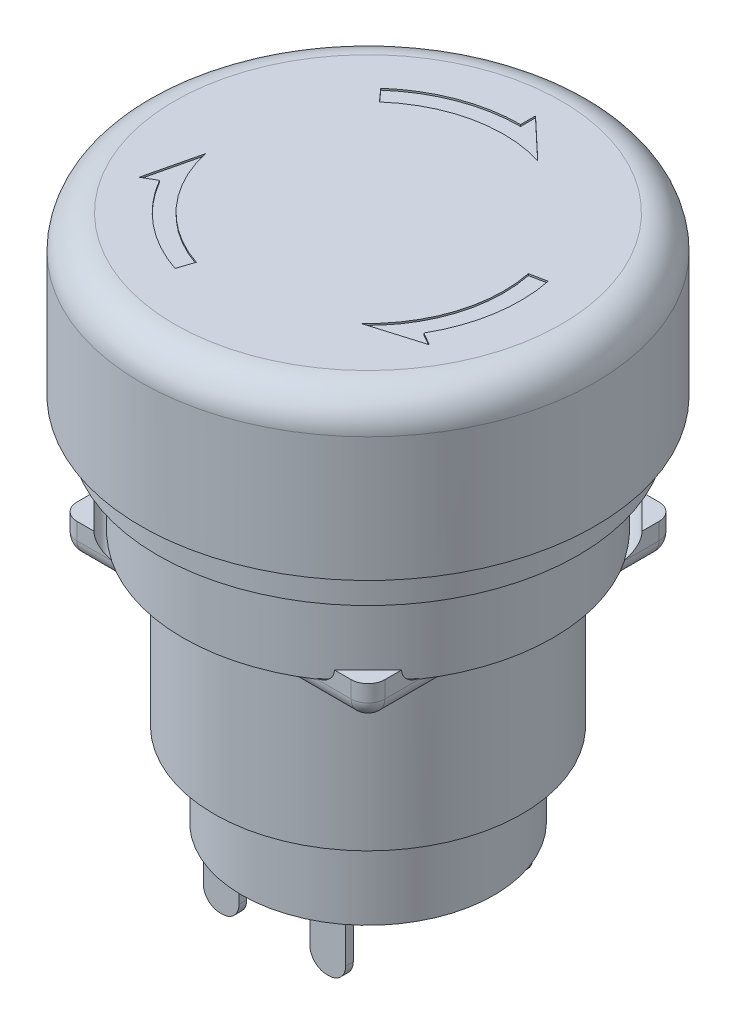
SolidWorks part; units mm, degrees
ref_plane "前视基准面" through (0, 0, 0) normal (0, 0, 1) x (1, 0, 0)
ref_plane "上视基准面" through (0, 0, 0) normal (0, 1, 0) x (1, 0, 0)
ref_plane "右视基准面" through (0, 0, 0) normal (1, 0, 0) x (0, 0, -1)
sketch "草图1" plane through (0, 0, 0) normal (0, 1, 0) x (1, 0, 0)
  circle A0 centre (0, 0) radius 7.5
  dimension "D1" = 15
extrude "凸台-拉伸1" add sketch "草图1" along normal blind 5
sketch "草图2" plane through (0, 0, 0) normal (0, -1, 0) x (1, 0, 0)
  line L0 (0, 0) -> (0, 7.5) construction
  line L1 (-4.2318, 5.5619) -> (-2.1076, 5.5619)
  line L2 (-4.2318, 5.5619) -> (-4.2318, 5.1067)
  line L3 (-4.2318, 5.1067) -> (-2.1076, 5.1067)
  line L4 (-2.1076, 5.5619) -> (-2.1076, 5.1067)
  line L5 (-4.2318, 5.5619) -> (-2.1076, 5.1067) construction
  line L6 (-4.2318, 5.1067) -> (-2.1076, 5.5619) construction
  line L7 (0, 0) -> (-7.5, 0) construction
  line L8 (4.2318, 5.1067) -> (2.1076, 5.5619) construction
  line L9 (4.2318, 5.5619) -> (2.1076, 5.1067) construction
  line L10 (2.1076, 5.5619) -> (2.1076, 5.1067)
  line L11 (4.2318, 5.1067) -> (2.1076, 5.1067)
  line L12 (4.2318, 5.5619) -> (4.2318, 5.1067)
  line L13 (4.2318, 5.5619) -> (2.1076, 5.5619)
  line L14 (4.2318, -5.5619) -> (2.1076, -5.1067) construction
  line L15 (4.2318, -5.1067) -> (2.1076, -5.5619) construction
  line L16 (4.2318, -5.5619) -> (2.1076, -5.5619)
  line L17 (4.2318, -5.5619) -> (4.2318, -5.1067)
  line L18 (2.1076, -5.5619) -> (2.1076, -5.1067)
  line L19 (-4.2318, -5.1067) -> (-2.1076, -5.5619) construction
  line L20 (-4.2318, -5.5619) -> (-2.1076, -5.1067) construction
  line L21 (-2.1076, -5.5619) -> (-2.1076, -5.1067)
  line L22 (-4.2318, -5.5619) -> (-4.2318, -5.1067)
  line L23 (-4.2318, -5.5619) -> (-2.1076, -5.5619)
  line L24 (4.2318, -5.1067) -> (2.1076, -5.1067)
  line L25 (-4.2318, -5.1067) -> (-2.1076, -5.1067)
  circle A0 centre (0, 0) radius 7.5 construction
  point P0 (-3.1697, 5.3343)
  point P16 (3.1697, 5.3343)
  point P21 (3.1697, -5.3343)
  point P26 (-3.1697, -5.3343)
extrude "凸台-拉伸2" add sketch "草图2" along normal blind 3.5
fillet "圆角1" radius 1 8 edges at (-4.2318, -3.5, -5.3343) (-2.1076, -3.5, -5.3343) (2.1076, -3.5, -5.3343) (4.2318, -3.5, -5.3343) (4.2318, -3.5, 5.3343) (2.1076, -3.5, 5.3343) (-2.1076, -3.5, 5.3343) (-4.2318, -3.5, 5.3343)
sketch "草图4" plane through (0, 5, 0) normal (0, 1, 0) x (1, 0, 0)
  circle A0 centre (0, 0) radius 9.15
  dimension "D1" = 18.3
extrude "凸台-拉伸3" add sketch "草图4" along normal blind 9
sketch "草图5" plane through (0, 14, 0) normal (0, 1, 0) x (1, 0, 0)
  line L1 (9.15, -9.15) -> (-9.15, -9.15)
  line L2 (9.15, -9.15) -> (9.15, 9.15)
  line L3 (9.15, 9.15) -> (-9.15, 9.15)
  line L4 (-9.15, -9.15) -> (-9.15, 9.15)
  line L5 (9.15, -9.15) -> (-9.15, 9.15) construction
  line L6 (9.15, 9.15) -> (-9.15, -9.15) construction
  circle A0 centre (0, 0) radius 9.15 construction
  point P0 (0, 0)
extrude "凸台-拉伸4" add sketch "草图5" along normal blind 1
sketch "草图6" plane through (0, 15, 0) normal (0, 1, 0) x (1, 0, 0)
  line L0 (-9.15, 9.15) -> (-7.15, 9.15)
  line L1 (9.15, 9.15) -> (-9.15, 9.15) construction
  line L2 (-7.15, 9.15) -> (-9.15, 7.15)
  line L3 (-9.15, 9.15) -> (-9.15, -9.15) construction
  line L4 (-9.15, 7.15) -> (-9.15, 9.15)
  line L5 (0, 0) -> (0, 7.15) construction
  line L6 (0, 0) -> (-9.15, 0) construction
  line L7 (9.15, 7.15) -> (9.15, 9.15)
  line L8 (7.15, 9.15) -> (9.15, 7.15)
  line L9 (9.15, 9.15) -> (7.15, 9.15)
  line L10 (9.15, -9.15) -> (7.15, -9.15)
  line L11 (7.15, -9.15) -> (9.15, -7.15)
  line L12 (9.15, -7.15) -> (9.15, -9.15)
  line L13 (-9.15, -7.15) -> (-9.15, -9.15)
  line L14 (-7.15, -9.15) -> (-9.15, -7.15)
  line L15 (-9.15, -9.15) -> (-7.15, -9.15)
  dimension "D1" = 2
  dimension "D2" = 2
extrude "凸台-拉伸5" add sketch "草图6" along normal blind 1
fillet "圆角2" radius 1 4 edges at (8.15, 15, 8.15) (8.15, 15, -8.15) (-8.15, 15, -8.15) (-8.15, 15, 8.15)
fillet "圆角3" radius 1 4 edges at (9.15, 15, -9.15) (-9.15, 15, -9.15) (-9.15, 15, 9.15) (9.15, 15, 9.15)
fillet "圆角4" radius 1 12 edges at (-4.075, 14, 9.15) (4.075, 14, 9.15) (8.8571, 14, 8.8571) (9.15, 14, 4.075) (9.15, 14, -4.075) (8.8571, 14, -8.8571) (4.075, 14, -9.15) (-4.075, 14, -9.15) (-8.8571, 14, -8.8571) (-9.15, 14, -4.075) (-9.15, 14, 4.075) (-8.8571, 14, 8.8571)
sketch "草图7" plane through (0, 15, 0) normal (0, 1, 0) x (1, 0, 0)
  circle A0 centre (0, 0) radius 11
  dimension "D1" = 22
extrude "凸台-拉伸6" add sketch "草图7" along normal blind 5
sketch "草图8" plane through (0, 20, 0) normal (0, 1, 0) x (1, 0, 0)
  circle A0 centre (0, 0) radius 13.5
  dimension "D1" = 27
extrude "凸台-拉伸7" add sketch "草图8" along normal blind 11.4
fillet "圆角5" radius 2 1 edges at (0, 31.4, 13.5)
sketch "草图9" plane through (0, 20, 0) normal (0, -1, 0) x (1, 0, 0)
  circle A0 centre (0, 0) radius 12.5
  dimension "D1" = 25
extrude "切除-拉伸1" cut sketch "草图9" against normal blind 2 flip side to cut
sketch "草图10" plane through (0, 31.4, 0) normal (0, 1, 0) x (1, 0, 0)
  line L0 (0, 9.0737) -> (0, 9.9619)
  line L1 (0, 9.9619) -> (2.376, 7.7162)
  line L2 (-5.3606, 6.0373) -> (-6.0245, 6.7851)
  line L3 (8.6273, -4.981) -> (5.4944, -5.9158)
  line L4 (7.8581, -4.5369) -> (8.6273, -4.981)
  line L5 (7.9088, 1.6237) -> (8.8883, 1.8248)
  line L6 (-8.6273, -4.981) -> (-7.8704, -1.8004)
  line L7 (-7.8581, -4.5369) -> (-8.6273, -4.981)
  line L8 (-2.5482, -7.661) -> (-2.8638, -8.6099)
  arc A0 (2.376, 7.7162) -> (-5.3606, 6.0373) centre (0, 0) ccw
  arc A1 (0, 9.0737) -> (-6.0245, 6.7851) centre (0, 0) ccw
  circle A2 centre (0, 0) radius 8.0737 construction
  circle A3 centre (0, 0) radius 9.0737 construction
  arc A4 (5.4944, -5.9158) -> (7.9088, 1.6237) centre (0, 0) ccw
  arc A5 (7.8581, -4.5369) -> (8.8883, 1.8248) centre (0, 0) ccw
  arc A6 (-7.8704, -1.8004) -> (-2.5482, -7.661) centre (0, 0) ccw
  arc A7 (-7.8581, -4.5369) -> (-2.8638, -8.6099) centre (0, 0) ccw
  point P22 (0, 0)
  dimension "D1" = 1
  dimension "D2" = 3
extrude "切除-拉伸2" cut sketch "草图10" against normal blind 0.1
